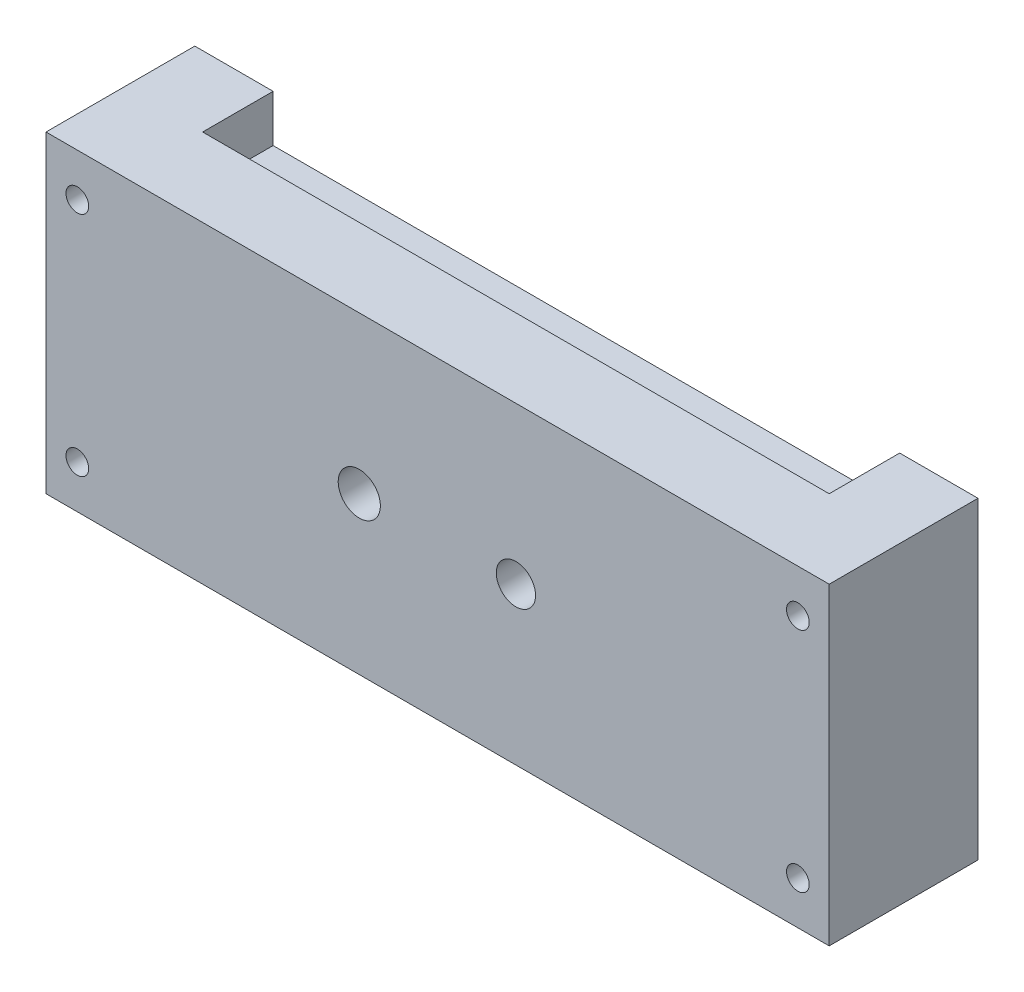
SolidWorks part; units mm, degrees
ref_plane "Front Plane" through (0, 0, 0) normal (0, 0, 1) x (1, 0, 0)
ref_plane "Top Plane" through (0, 0, 0) normal (0, 1, 0) x (1, 0, 0)
ref_plane "Right Plane" through (0, 0, 0) normal (1, 0, 0) x (0, 0, -1)
sketch "Sketch1" plane through (0, 0, 0) normal (0, 0, 1) x (1, 0, 0)
  line L1 (-33.75, 21.5625) -> (66.25, 21.5625)
  line L2 (-33.75, 21.5625) -> (-33.75, -18.4375)
  line L3 (-33.75, -18.4375) -> (66.25, -18.4375)
  line L4 (66.25, 21.5625) -> (66.25, -18.4375)
  dimension "D1" = 100
  dimension "D2" = 40
extrude "Boss-Extrude1" add sketch "Sketch1" along normal blind 38
sketch "Sketch2" plane through (0, 0, 0) normal (0, 0, -1) x (-1, 0, 0)
  line L0 (-66.25, -18.4375) -> (-66.25, 21.5625) construction
  line L1 (-58.25, 18.5625) -> (-18.75, 18.5625)
  line L2 (-58.25, 18.5625) -> (-58.25, -15.4375)
  line L3 (-58.25, -15.4375) -> (-18.75, -15.4375)
  line L4 (-18.75, 18.5625) -> (-18.75, -15.4375)
  line L5 (-13.75, 18.5625) -> (25.75, 18.5625)
  line L6 (-13.75, 18.5625) -> (-13.75, -15.4375)
  line L7 (-13.75, -15.4375) -> (25.75, -15.4375)
  line L8 (25.75, 18.5625) -> (25.75, -15.4375)
  line L9 (33.75, 21.5625) -> (33.75, -18.4375) construction
  line L10 (-66.25, 21.5625) -> (33.75, 21.5625) construction
  line L11 (33.75, -18.4375) -> (-66.25, -18.4375) construction
  dimension "D1" = 8
  dimension "D2" = 8
  dimension "D3" = 5
  dimension "D4" = 3
  dimension "D5" = 3
  dimension "D6" = 3
  dimension "D7" = 3
  dimension "D8" = 39.5
  dimension "D9" = 39.5
extrude "Cut-Extrude2" [suppressed] cut sketch "Sketch2" against normal blind 21 from offset 12 offset against normal yes
sketch "Sketch4" plane through (0, 0, 0) normal (0, 0, -1) x (-1, 0, 0)
  line L0 (-66.25, -18.4375) -> (-66.25, 21.5625) construction
  line L1 (33.75, 21.5625) -> (33.75, -18.4375) construction
  line L2 (-66.25, 21.5625) -> (33.75, 21.5625) construction
  line L3 (33.75, -18.4375) -> (-66.25, -18.4375) construction
  circle A0 centre (-62.25, 16.0625) radius 1.45
  circle A1 centre (-62.25, -12.9375) radius 1.45
  circle A2 centre (29.75, 16.0625) radius 1.45
  circle A3 centre (29.75, -12.9375) radius 1.45
  dimension "D1" = 4
  dimension "D2" = 4
  dimension "D3" = 5.5
  dimension "D4" = 5.5
extrude "Cut-Extrude4" cut sketch "Sketch4" against normal up to next
sketch "Sketch6" plane through (0, 21.5625, 0) normal (0, 1, 0) x (1, 0, 0)
  line L0 (-33.75, -38) -> (-33.75, 0) construction
  line L1 (66.25, -38) -> (-33.75, -38)
  line L2 (66.25, -38) -> (66.25, -19)
  line L3 (66.25, -19) -> (-33.75, -19)
  line L4 (-33.75, -38) -> (-33.75, -19)
extrude "Cut-Extrude5" cut sketch "Sketch6" against normal through all
fillet "Fillet1" [suppressed] radius 0.5
sketch "Sketch10" [suppressed] plane through (0, 0, 12) normal (0, 0, 1) x (1, 0, 0)
  line L8 (14.25, -14.9375) -> (14.25, 18.0625)
  line L9 (13.25, 19.0625) -> (-25.25, 19.0625)
  line L10 (-26.25, 18.0625) -> (-26.25, -14.9375)
  line L11 (-25.25, -15.9375) -> (13.25, -15.9375)
  line L12 (14.25, -14.9375) -> (14.25, 18.0625)
  line L13 (13.25, 19.0625) -> (-25.25, 19.0625)
  line L14 (-26.25, 18.0625) -> (-26.25, -14.9375)
  line L15 (-25.25, -15.9375) -> (13.25, -15.9375)
  arc A8 (14.25, 18.0625) -> (13.25, 19.0625) centre (13.25, 18.0625) ccw
  arc A9 (-25.25, 19.0625) -> (-26.25, 18.0625) centre (-25.25, 18.0625) ccw
  arc A10 (-26.25, -14.9375) -> (-25.25, -15.9375) centre (-25.25, -14.9375) ccw
  arc A11 (13.25, -15.9375) -> (14.25, -14.9375) centre (13.25, -14.9375) ccw
  arc A12 (14.25, 18.0625) -> (13.25, 19.0625) centre (13.25, 18.0625) ccw
  arc A13 (-25.25, 19.0625) -> (-26.25, 18.0625) centre (-25.25, 18.0625) ccw
  arc A14 (-26.25, -14.9375) -> (-25.25, -15.9375) centre (-25.25, -14.9375) ccw
  arc A15 (13.25, -15.9375) -> (14.25, -14.9375) centre (13.25, -14.9375) ccw
  dimension "D1" = 0.5
sketch "Sketch11" [suppressed] plane through (0, 0, 12) normal (0, 0, 1) x (1, 0, 0)
  line L8 (58.75, -14.9375) -> (58.75, 18.0625)
  line L9 (57.75, 19.0625) -> (19.25, 19.0625)
  line L10 (18.25, 18.0625) -> (18.25, -14.9375)
  line L11 (19.25, -15.9375) -> (57.75, -15.9375)
  line L12 (58.75, -14.9375) -> (58.75, 18.0625)
  line L13 (57.75, 19.0625) -> (19.25, 19.0625)
  line L14 (18.25, 18.0625) -> (18.25, -14.9375)
  line L15 (19.25, -15.9375) -> (57.75, -15.9375)
  arc A8 (58.75, 18.0625) -> (57.75, 19.0625) centre (57.75, 18.0625) ccw
  arc A9 (19.25, 19.0625) -> (18.25, 18.0625) centre (19.25, 18.0625) ccw
  arc A10 (18.25, -14.9375) -> (19.25, -15.9375) centre (19.25, -14.9375) ccw
  arc A11 (57.75, -15.9375) -> (58.75, -14.9375) centre (57.75, -14.9375) ccw
  arc A12 (58.75, 18.0625) -> (57.75, 19.0625) centre (57.75, 18.0625) ccw
  arc A13 (19.25, 19.0625) -> (18.25, 18.0625) centre (19.25, 18.0625) ccw
  arc A14 (18.25, -14.9375) -> (19.25, -15.9375) centre (19.25, -14.9375) ccw
  arc A15 (57.75, -15.9375) -> (58.75, -14.9375) centre (57.75, -14.9375) ccw
  dimension "D1" = 0.5
sketch "Sketch17" plane through (0, 0, 0) normal (0, 0, -1) x (-1, 0, 0)
  line L0 (-66.25, 1.5625) -> (33.75, 1.5625) construction
  line L3 (-16.25, 21.5625) -> (-16.25, -18.4375) construction
  line L4 (-66.25, 21.5625) -> (33.75, 21.5625) construction
  line L5 (33.75, -18.4375) -> (-66.25, -18.4375) construction
  line L6 (-66.25, -18.4375) -> (-66.25, 21.5625) construction
  line L9 (33.75, 21.5625) -> (33.75, -18.4375) construction
  line L10 (-56.25, 1.5625) -> (23.75, 1.5625) construction
  line L11 (-56.25, 9.0625) -> (23.75, 9.0625)
  line L12 (-56.25, -5.9375) -> (23.75, -5.9375)
  arc A2 (-56.25, 9.0625) -> (-56.25, -5.9375) centre (-56.25, 1.5625) ccw
  arc A3 (23.75, -5.9375) -> (23.75, 9.0625) centre (23.75, 1.5625) ccw
  point P15 (-16.25, 1.5625)
extrude "Cut-Extrude12" cut sketch "Sketch17" against normal blind 9
sketch "Sketch18" plane through (0, 0, 9) normal (0, 0, -1) x (-1, 0, 0)
  line L0 (-66.25, 1.5625) -> (33.75, 1.5625) construction
  line L1 (-66.25, -18.4375) -> (-66.25, 21.5625) construction
  line L2 (33.75, 21.5625) -> (33.75, -18.4375) construction
  line L3 (-16.25, 21.5625) -> (-16.25, -18.4375) construction
  line L4 (-66.25, 21.5625) -> (33.75, 21.5625) construction
  line L5 (33.75, -18.4375) -> (-66.25, -18.4375) construction
  circle A0 centre (-26.25, 1.5625) radius 2.5069
  circle A1 centre (-6.25, 1.5625) radius 2.6931
  dimension "D1" = 20
  dimension "D2" = 10
  dimension "D3" = 10
extrude "Cut-Extrude13" cut sketch "Sketch18" against normal up to next
sketch "Sketch19" plane through (0, 0, 9) normal (0, 0, -1) x (-1, 0, 0)
  circle A0 centre (-26.25, 1.5625) radius 4.572
  circle A1 centre (-26.25, 1.5625) radius 6.477
  circle A2 centre (-6.25, 1.5625) radius 4.572
  circle A3 centre (-6.25, 1.5625) radius 6.477
  dimension "D1" = 9.144
  dimension "D2" = 12.954
  dimension "D3" = 12.954
  dimension "D4" = 9.144
extrude "Cut-Extrude14" cut sketch "Sketch19" against normal blind 0.7937 contours A1 A0 | A3 A2 region at (32.5438, 1.5625, 9) region at (12.5438, 1.5625, 9)
sketch "Sketch20" plane through (-33.75, 0, 0) normal (-1, 0, 0) x (0, 0, 1)
  line L0 (0, 12.0625) -> (-2, 12.0625)
  line L1 (0, 21.5625) -> (0, -18.4375) construction
  line L2 (-2, 12.0625) -> (-2, 9.0625)
  line L8 (9, 9.0625) -> (9, -5.9375) construction
  line L9 (9, 1.5625) -> (-12.0371, 1.5625) construction
  line L10 (-2, -8.9375) -> (-2, -5.9375)
  line L15 (0, -8.9375) -> (-2, -8.9375)
  line L16 (-2, 9.0625) -> (0, 9.0625)
  line L17 (0, 9.0625) -> (0, 12.0625)
  line L18 (-2, -5.9375) -> (0, -5.9375)
  line L19 (0, -5.9375) -> (0, -8.9375)
  dimension "D4" = 3
  dimension "D5" = 2
sketch "Sketch21" plane through (0, 0, 0) normal (0, 0, -1) x (-1, 0, 0)
  line L0 (33.75, 21.5625) -> (33.75, -18.4375) construction
  line L1 (23.75, 9.0625) -> (33.75, 9.0625)
  line L2 (23.75, 9.0625) -> (23.75, -5.9375)
  line L3 (23.75, -5.9375) -> (33.75, -5.9375)
  line L4 (33.75, 9.0625) -> (33.75, -5.9375)
extrude "Cut-Extrude15" cut sketch "Sketch21" against normal up to surface (9 mm away) up to face at (19.773, 1.5625, 9)
sketch "Sketch22" plane through (-33.75, 0, 0) normal (-1, 0, 0) x (0, 0, 1)
  line L0 (9, 1.5625) -> (-10.0634, 1.5625) construction
  line L1 (9, 9.0625) -> (9, -5.9375) construction
  line L2 (9, 9.0625) -> (0, 9.0625) construction
  line L3 (2, 9.0625) -> (6, 9.0625)
  line L4 (2, 9.0625) -> (2, 11.5625)
  line L5 (2, 11.5625) -> (6, 11.5625)
  line L6 (6, 9.0625) -> (6, 11.5625)
  line L7 (2, -5.9375) -> (2, -8.4375)
  line L8 (2, -5.9375) -> (6, -5.9375)
  line L9 (6, -5.9375) -> (6, -8.4375)
  line L10 (2, -8.4375) -> (6, -8.4375)
  line L11 (0, 21.5625) -> (0, 9.0625) construction
  dimension "D1" = 4
  dimension "D2" = 2.5
  dimension "D3" = 2
extrude "Cut-Extrude16" cut sketch "Sketch22" against normal blind 90
sketch "Sketch23" plane through (0, 0, 0) normal (0, 0, -1) x (-1, 0, 0)
  line L0 (-63.75, 1.5625) -> (37.5576, 1.5625) construction
  line L1 (-66.25, 21.5625) -> (33.75, 21.5625) construction
  line L2 (-56.25, 21.5625) -> (23.75, 21.5625)
  line L3 (-56.25, 21.5625) -> (-56.25, 15.5625)
  line L4 (-56.25, 15.5625) -> (23.75, 15.5625)
  line L5 (23.75, 21.5625) -> (23.75, 15.5625)
  line L6 (-56.25, -18.4375) -> (-56.25, -12.4375)
  line L7 (-56.25, -18.4375) -> (23.75, -18.4375)
  line L8 (23.75, -18.4375) -> (23.75, -12.4375)
  line L9 (-56.25, -12.4375) -> (23.75, -12.4375)
  line L10 (33.75, 21.5625) -> (33.75, 9.0625) construction
  arc A0 (-56.25, 9.0625) -> (-56.25, -5.9375) centre (-56.25, 1.5625) ccw construction
  dimension "D1" = 80
  dimension "D2" = 10
  dimension "D3" = 6
extrude "Cut-Extrude17" cut sketch "Sketch23" against normal blind 9
